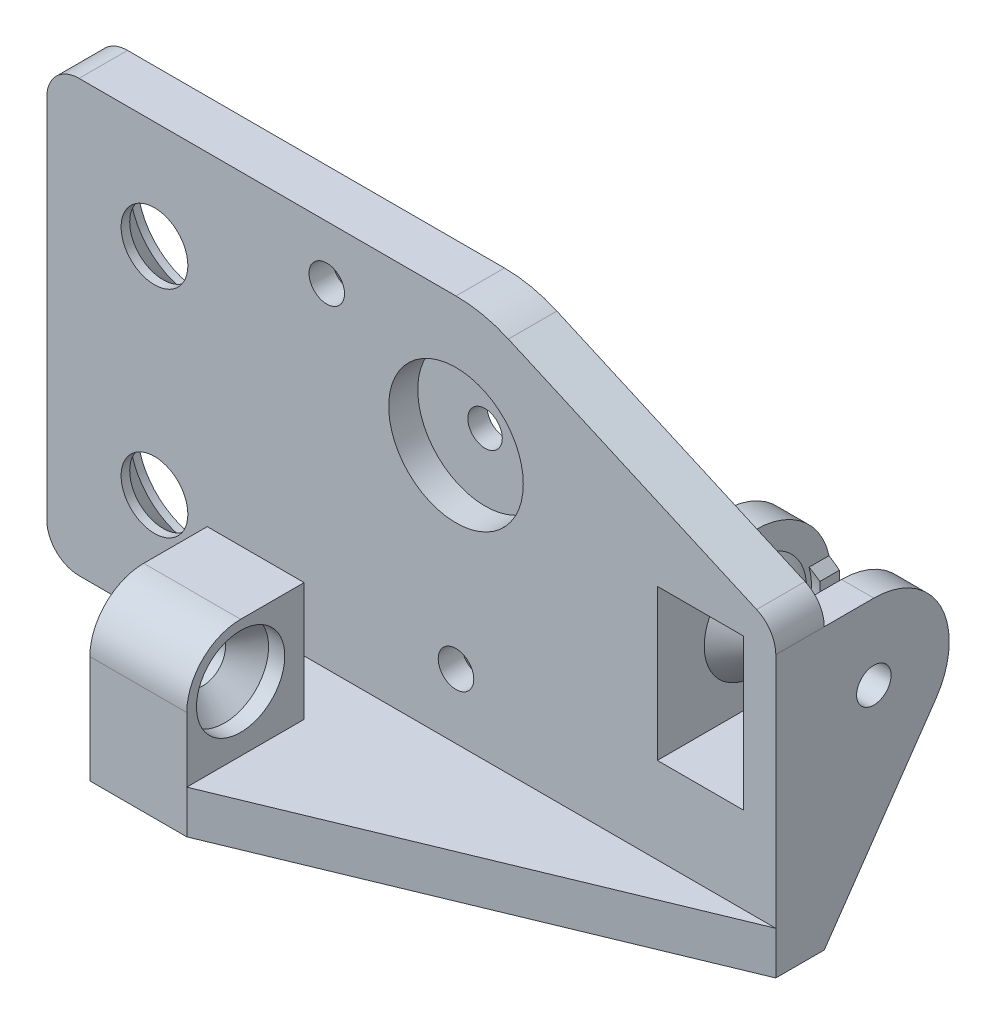
SolidWorks part; units mm, degrees
material "Custom Plastic"
ref_plane "Front Plane" through (0, 0, 0) normal (0, 0, 1) x (1, 0, 0)
ref_plane "Top Plane" through (0, 0, 0) normal (0, 1, 0) x (1, 0, 0)
ref_plane "Right Plane" through (0, 0, 0) normal (1, 0, 0) x (0, 0, -1)
sketch "Sketch1" plane through (0, 0, 0) normal (0, 0, 1) x (1, 0, 0)
  line L0 (-10, -20) -> (-10, 0) construction
  line L1 (-10, -20) -> (10, -20) construction
  line L2 (-10, 0) -> (10, 0) construction
  line L3 (10, -20) -> (10, 0) construction
  line L4 (-10, -20) -> (10, 0) construction
  line L5 (-10, 0) -> (10, -20) construction
  line L6 (-10, 0) -> (-10, 20) construction
  line L7 (-10, 17) -> (-10, -17)
  line L8 (-10, 20) -> (10, 20) construction
  line L9 (10, 0) -> (10, 20) construction
  line L10 (-10, 0) -> (10, 20) construction
  line L11 (-10, 20) -> (10, 0) construction
  line L12 (-7, 20) -> (10, 20)
  line L13 (57.7, 20) -> (57.7, -20)
  line L15 (10, 20) -> (57.7, 20)
  line L18 (57.7, -20) -> (-7, -20)
  circle A0 centre (0, 10) radius 3.1
  circle A1 centre (0, -10) radius 3.1
  arc A2 (-7, 20) -> (-10, 17) centre (-7, 17) ccw
  arc A3 (-10, -17) -> (-7, -20) centre (-7, -17) ccw
  circle A4 centre (28, 8) radius 1.6
  point P0 (0, 10)
  point P1 (0, -10)
  dimension "D2" = 6.2
  dimension "D6" = 3
  dimension "D4" = 3.2
  dimension "D1" = 20
  dimension "D3" = 57.7
  dimension "D5" = 18
  dimension "D7" = 8
extrude "Boss-Extrude1" add sketch "Sketch1" along normal blind 4.5
sketch "Sketch2" plane through (0, -20, 0) normal (0, -1, 0) x (1, 0, 0)
  line L0 (10, 4.5) -> (10, 20.5)
  line L1 (-7, 4.5) -> (57.7, 4.5) construction
  line L2 (10, 20.5) -> (19, 20.5)
  line L3 (19, 20.5) -> (57.7, 4.5)
  line L4 (57.7, 4.5) -> (10, 4.5)
  dimension "D1" = 16
  dimension "D2" = 10
  dimension "D3" = 9
extrude "Boss-Extrude2" add sketch "Sketch2" against normal blind 15
sketch "Sketch3" plane through (57.7, 0, 0) normal (1, 0, 0) x (0, 0, -1)
  line L0 (4.6036, 6) -> (0, 6)
  line L1 (0, -20) -> (0, 20) construction
  line L2 (0, 6) -> (0, -20)
  line L4 (0, -20) -> (10.3655, -4.975)
  arc A0 (10.3655, -4.975) -> (4.6036, 6) centre (4.6036, -1) ccw
  dimension "D1" = 7
  dimension "D2" = 1
extrude "Boss-Extrude3" add sketch "Sketch3" against normal blind 14
sketch "Sketch4" plane through (0, -5, 0) normal (0, 1, 0) x (1, 0, 0)
  line L0 (57.7, -4.5) -> (57.7, 0) construction
  line L1 (10, -4.5) -> (57.7, -4.5)
  line L2 (10, -4.5) -> (10, -9.6)
  line L3 (10, -9.6) -> (19, -9.6)
  line L4 (57.7, -4.5) -> (57.7, -20.5)
  line L5 (19, -20.5) -> (19, -9.6)
  line L6 (19, -20.5) -> (57.7, -20.5)
  dimension "D1" = 5.1
extrude "Cut-Extrude1" cut sketch "Sketch4" against normal offset from surface (11 mm away) 4 contours L6 L4 L1 L2 L3 L5 up to face at (17.9063, -20, 7.8125)
sketch "Sketch5" plane through (57.7, 0, 0) normal (1, 0, 0) x (0, 0, -1)
  circle A0 centre (4.6036, -1) radius 1.6
  dimension "D1" = 3.2
extrude "Cut-Extrude2" cut sketch "Sketch5" against normal through all
sketch "Sketch6" plane through (57.7, 0, 0) normal (1, 0, 0) x (0, 0, -1)
  line L0 (0.7145, 2.8891) -> (8.8191, 10.9937)
  line L1 (8.8191, 10.9937) -> (8.8191, -12.9937)
  line L2 (8.8191, -12.9937) -> (0.7145, -4.8891)
  arc A0 (0.7145, 2.8891) -> (0.7145, -4.8891) centre (4.6036, -1) ccw
  dimension "D1" = 5.5
extrude "Cut-Extrude3" cut sketch "Sketch6" against normal blind 8 from offset 3 offset against normal yes
fillet "Fillet1" radius 5 1 edges at (14.5, -5, 20.5)
sketch "Sketch7" plane through (19, 0, 0) normal (1, 0, 0) x (0, 0, -1)
  line L0 (-4.5, -20) -> (-20.5, -20) construction
  line L1 (-20.5, -10) -> (-20.5, -16) construction
  circle A0 centre (-15.5, -10) radius 2.1
  dimension "D1" = 4.2
  dimension "D2" = 10
  dimension "D3" = 5
extrude "Cut-Extrude4" cut sketch "Sketch7" against normal through all
sketch "Sketch8" plane through (19, 0, 0) normal (1, 0, 0) x (0, 0, -1)
  circle A0 centre (-15.5, -10) radius 4.1
  dimension "D1" = 8.2
extrude "Cut-Extrude5" cut sketch "Sketch8" against normal offset from surface (1.5 mm away) 7.5 up to face at (10, -12.1, 15.5)
chamfer "Chamfer1" distance 2 angle 45 1 edges at (17.5, -12.1, 15.5)
ref_axis "Axis1" through (54.7, -1, -4.6036) along (1, 0, 0)
sketch "Sketch9" plane through (0, 0, 4.5) normal (0, 0, 1) x (1, 0, 0)
  line L0 (46.7, -4.8891) -> (46.7, 2.8891) construction
  line L1 (46.7, 6) -> (54.7, 6)
  line L2 (46.7, 6) -> (46.7, 3.5)
  line L3 (46.7, 3.5) -> (54.7, 3.5) construction
  line L4 (54.7, 6) -> (54.7, 3.5)
  line L5 (54.7, 2.8891) -> (54.7, -4.8891) construction
  line L6 (54.7, -4.8891) -> (54.7, -10.6352) construction
  line L7 (46.7, -5.5) -> (54.7, -5.5) construction
  line L8 (46.7, -5.5) -> (46.7, -8)
  line L9 (46.7, -8) -> (54.7, -8)
  line L10 (54.7, -5.5) -> (54.7, -8)
  line L11 (54.7, 3.5) -> (54.7, -5.5)
  line L12 (54.7, -1) -> (57.7, -1) construction
  line L13 (46.7, 3.5) -> (46.7, -5.5)
  point P14 (54.7, -1)
  dimension "D1" = 2.5
  dimension "D2" = 9
extrude "Cut-Extrude6" cut sketch "Sketch9" against normal through all
sketch "Sketch10" plane through (0, 0, 0) normal (0, 0, -1) x (-1, 0, 0)
  line L1 (-57.7, 6) -> (-57.7, 20)
  line L2 (-57.7, 20) -> (-28, 20)
  line L3 (-55.9166, 8.7422) -> (-32.8666, 18.9689)
  arc A0 (-28, 20) -> (-32.8666, 18.9689) centre (-28, 8) ccw
  arc A1 (-55.9166, 8.7422) -> (-57.7, 6) centre (-54.7, 6) ccw
extrude "Cut-Extrude7" cut sketch "Sketch10" against normal through all
sketch "Sketch11" plane through (0, 0, 0) normal (0, 0, -1) x (-1, 0, 0)
  line L1 (-30.75, -8.4123) -> (-30.75, -11.5877) construction
  line L2 (-30.75, -11.5877) -> (-28, -13.1754) construction
  line L3 (-28, -13.1754) -> (-25.25, -11.5877) construction
  line L4 (-25.25, -11.5877) -> (-25.25, -8.4123) construction
  line L5 (-25.25, -8.4123) -> (-28, -6.8246) construction
  line L6 (-28, -6.8246) -> (-30.75, -8.4123) construction
  line L7 (-13.25, 13.4123) -> (-13.25, 16.5877) construction
  line L8 (-13.25, 16.5877) -> (-16, 18.1754) construction
  line L9 (-16, 18.1754) -> (-18.75, 16.5877) construction
  line L10 (-18.75, 16.5877) -> (-18.75, 13.4123) construction
  line L11 (-18.75, 13.4123) -> (-16, 11.8246) construction
  line L12 (-16, 11.8246) -> (-13.25, 13.4123) construction
  circle A0 centre (-16, 15) radius 1.65
  circle A1 centre (-28, -10) radius 1.65
  circle A2 centre (-28, -10) radius 2.75 construction
  circle A3 centre (-16, 15) radius 2.75 construction
  circle A4 centre (-28, 8) radius 1.6 construction
  point P20 (-28, 8)
  dimension "D1" = 3.3
  dimension "D2" = 5.5
  dimension "D6" = 10
  dimension "D3" = 12
  dimension "D4" = 15
extrude "Cut-Extrude9" cut sketch "Sketch11" against normal through all
sketch "Sketch13" plane through (46.7, 0, 0) normal (1, 0, 0) x (0, 0, -1)
  circle A0 centre (4.6036, -1) radius 2.75
  circle A1 centre (4.6036, -1) radius 1.6
  circle A4 centre (4.6036, -1) radius 1.6 construction
  point P9 (4.6036, -2.5)
  point P11 (10.6036, -2.5)
  point P12 (4.6036, 0.5)
  point P13 (10.6036, 0.5)
  dimension "D1" = 5.5
extrude "Boss-Extrude4" add sketch "Sketch13" along normal blind 2
sketch "Sketch15" plane through (46.7, 0, 0) normal (1, 0, 0) x (0, 0, -1)
  line L1 (9.5826, 0.5) -> (11.441, 0.5)
  line L3 (9.5826, -2.5) -> (11.441, -2.5)
  arc A0 (9.5826, -2.5) -> (9.5826, 0.5) centre (4.6036, -1) ccw
  arc A1 (11.441, -2.5) -> (11.441, 0.5) centre (4.6036, -1) ccw
  arc A2 (10.3655, -4.975) -> (4.6036, 6) centre (4.6036, -1) ccw construction
  dimension "D1" = 5.2
  dimension "D2" = 3
extrude "Boss-Extrude5" add sketch "Sketch15" along normal blind 0.825
ref_plane "Plane1" through (50.7, 0, 0) normal (1, 0, 0) x (0, 0, -1)
mirror "Mirror1" about plane through (50.7, 0, 0) normal (1, 0, 0) of "Boss-Extrude5", "Boss-Extrude4"
chamfer "Chamfer3" distance 2 angle 45 2 edges at (54.7, 1.75, -4.6036) (46.7, 1.75, -4.6036)
sketch "Sketch14" plane through (0, 0, 0) normal (0, 0, -1) x (-1, 0, 0)
  circle A0 centre (0, -10) radius 6.1
  circle A1 centre (0, 10) radius 6.1
  dimension "D1" = 12.2
extrude "Cut-Extrude10" cut sketch "Sketch14" against normal blind 0.7
chamfer "Chamfer4" distance 3 angle 45 2 edges at (-3.1, -10, 0.7) (-3.1, 10, 0.7)
chamfer "Chamfer5" distance 0.83 angle 45 4 edges at (53.875, -2.5, -10.5118) (53.875, 0.5, -10.5118) (47.525, -2.5, -10.5118) (47.525, 0.5, -10.5118)
sketch "Sketch16" plane through (0, 0, 0) normal (0, 0, -1) x (-1, 0, 0)
  circle A0 centre (-28, -10) radius 3.4
  circle A1 centre (-16, 15) radius 3.4
  dimension "D1" = 6.8
extrude "Cut-Extrude11" cut sketch "Sketch16" against normal blind 0.5
chamfer "Chamfer6" distance 1.8 angle 45 2 edges at (26.35, -10, 0.5) (14.35, 15, 0.5)
sketch "Sketch17" plane through (10, 0, 0) normal (-1, 0, 0) x (0, 0, 1)
  line L0 (15.5, -10) -> (16.9849, -8.5151)
  line L1 (16.9849, -8.5151) -> (15.9498, -7.48)
  line L2 (15.9498, -7.48) -> (15.0502, -7.48)
  line L3 (15.0502, -7.48) -> (14.0151, -8.5151)
  line L4 (14.0151, -8.5151) -> (15.5, -10)
  circle A0 centre (15.5, -10) radius 2.1 construction
  point P0 (15.5, -7.9)
  dimension "D1" = 0.42
extrude "Cut-Extrude12" cut sketch "Sketch17" against normal through all
sketch "Sketch18" plane through (0, 0, 4.5) normal (0, 0, 1) x (1, 0, 0)
  circle A0 centre (28, 8) radius 6.25
  dimension "D1" = 12.5
extrude "Cut-Extrude13" cut sketch "Sketch18" against normal blind 2.7
equation "\"y-cross-rib-thickness\"=4"
equation "\"y-rib-thickness\"=6"
equation "\"bed-plate-thickness\"=3"
equation "\"x-plate-thickness\"=5"
equation "\"rod-diameter\"=12"
equation "\"t-nut-hole-diameter\"=3"
equation "\"y-plate-thickness\"=5"
equation "\"D1@Sketch4\"=\"y-plate-thickness\"+.1"
equation "\"D1@Boss-Extrude5\"=(8-6.35)/2"
